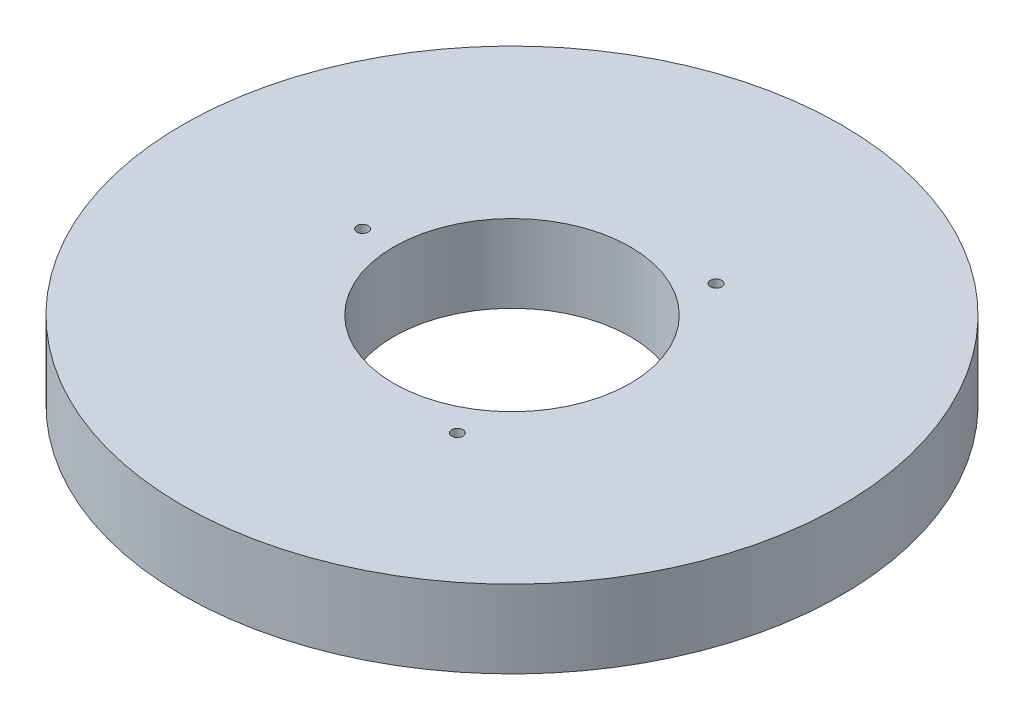
SolidWorks part; units mm, degrees
ref_plane "Front Plane" through (0, 0, 0) normal (0, 0, 1) x (1, 0, 0)
ref_plane "Top Plane" through (0, 0, 0) normal (0, 1, 0) x (1, 0, 0)
ref_plane "Right Plane" through (0, 0, 0) normal (1, 0, 0) x (0, 0, -1)
sketch "Sketch1" plane through (0, 0, 0) normal (0, 1, 0) x (1, 0, 0)
  circle A0 centre (0, 0) radius 97.5
  dimension "FLANGE_OD" = 195
extrude "Boss-Extrude1" add sketch "Sketch1" along normal blind 23
sketch "Sketch2" plane through (0, 0, 0) normal (0, 1, 0) x (1, 0, 0)
  circle A0 centre (0, 0) radius 35
  dimension "BORE_D" = 70
extrude "Cut-Extrude1" cut sketch "Sketch2" along normal through all
sketch "Sketch3" plane through (0, 23, 0) normal (0, 1, 0) x (1, 0, 0)
  circle A0 centre (0, 0) radius 44.1959 construction
  circle A1 centre (-44.1959, 0) radius 1.6684
  dimension "BOLT_D" = 3.3368
  dimension "BOLT_PCD" = 88.3917
extrude "Cut-Extrude2" cut sketch "Sketch3" against normal blind 21.9713
pattern_circular "CirPattern1" count 3 over 360 about axis through (0, 0, 0) along (0, 1, 0) of "Cut-Extrude2"
